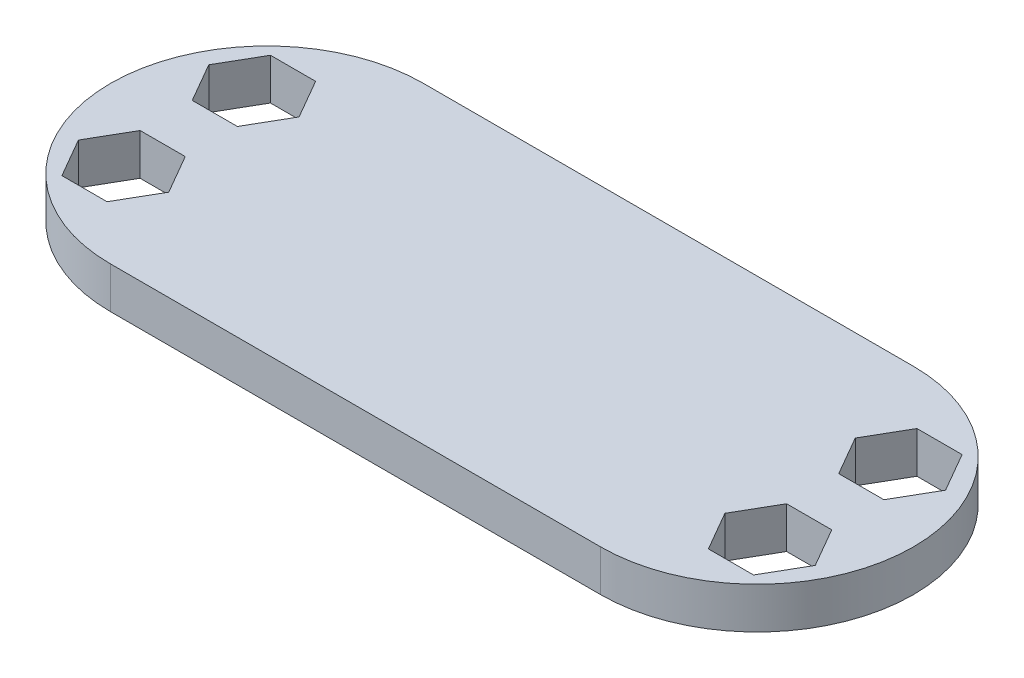
SolidWorks part; units mm, degrees
ref_plane "Front Plane" through (0, 0, 0) normal (0, 0, 1) x (1, 0, 0)
ref_plane "Top Plane" through (0, 0, 0) normal (0, 1, 0) x (1, 0, 0)
ref_plane "Right Plane" through (0, 0, 0) normal (1, 0, 0) x (0, 0, -1)
sketch "Sketch2" plane through (0, 0, 0) normal (0, 1, 0) x (1, 0, 0)
  line L0 (-145.5214, -2.0029) -> (-107.9214, -2.0029)
  line L2 (-145.5214, -26.0029) -> (-107.9214, -26.0029)
  line L4 (-151.5214, 3.0634) -> (-151.5214, -29.2944) construction
  line L9 (-101.9214, 1.8989) -> (-101.9214, -30.7894) construction
  line L10 (-126.7214, -2.0029) -> (-126.7214, -26.0029) construction
  line L11 (-149.7894, -12.0029) -> (-148.0573, -9.0029)
  line L12 (-148.0573, -9.0029) -> (-149.7894, -6.0029)
  line L13 (-149.7894, -6.0029) -> (-153.2535, -6.0029)
  line L14 (-153.2535, -6.0029) -> (-154.9855, -9.0029)
  line L15 (-154.9855, -9.0029) -> (-153.2535, -12.0029)
  line L16 (-153.2535, -12.0029) -> (-149.7894, -12.0029)
  line L17 (-157.5214, -14.0029) -> (-126.7214, -14.0029) construction
  line L18 (-153.2535, -16.0029) -> (-149.7894, -16.0029)
  line L19 (-154.9855, -19.0029) -> (-153.2535, -16.0029)
  line L20 (-153.2535, -22.0029) -> (-154.9855, -19.0029)
  line L21 (-149.7894, -22.0029) -> (-153.2535, -22.0029)
  line L22 (-148.0573, -19.0029) -> (-149.7894, -22.0029)
  line L23 (-149.7894, -16.0029) -> (-148.0573, -19.0029)
  line L24 (-103.6535, -16.0029) -> (-105.3855, -19.0029)
  line L25 (-105.3855, -19.0029) -> (-103.6535, -22.0029)
  line L26 (-103.6535, -22.0029) -> (-100.1894, -22.0029)
  line L27 (-100.1894, -22.0029) -> (-98.4573, -19.0029)
  line L28 (-98.4573, -19.0029) -> (-100.1894, -16.0029)
  line L29 (-100.1894, -16.0029) -> (-103.6535, -16.0029)
  line L30 (-100.1894, -12.0029) -> (-103.6535, -12.0029)
  line L31 (-98.4573, -9.0029) -> (-100.1894, -12.0029)
  line L32 (-100.1894, -6.0029) -> (-98.4573, -9.0029)
  line L33 (-103.6535, -6.0029) -> (-100.1894, -6.0029)
  line L34 (-105.3855, -9.0029) -> (-103.6535, -6.0029)
  line L35 (-103.6535, -12.0029) -> (-105.3855, -9.0029)
  arc A0 (-145.5214, -2.0029) -> (-145.5214, -26.0029) centre (-145.5214, -14.0029) ccw
  arc A7 (-107.9214, -26.0029) -> (-107.9214, -2.0029) centre (-107.9214, -14.0029) ccw
  circle A8 centre (-151.5214, -9.0029) radius 3 construction
  circle A9 centre (-151.5214, -19.0029) radius 3 construction
  circle A10 centre (-101.9214, -19.0029) radius 3 construction
  circle A11 centre (-101.9214, -9.0029) radius 3 construction
  dimension "D5" = 24.8
  dimension "D4" = 6
  dimension "D1" = 24
  dimension "D2" = 6
  dimension "D3" = 5
  dimension "D9" = 6
  dimension "D10" = 0
extrude "Boss-Extrude1" add sketch "Sketch2" along normal blind 3.175
